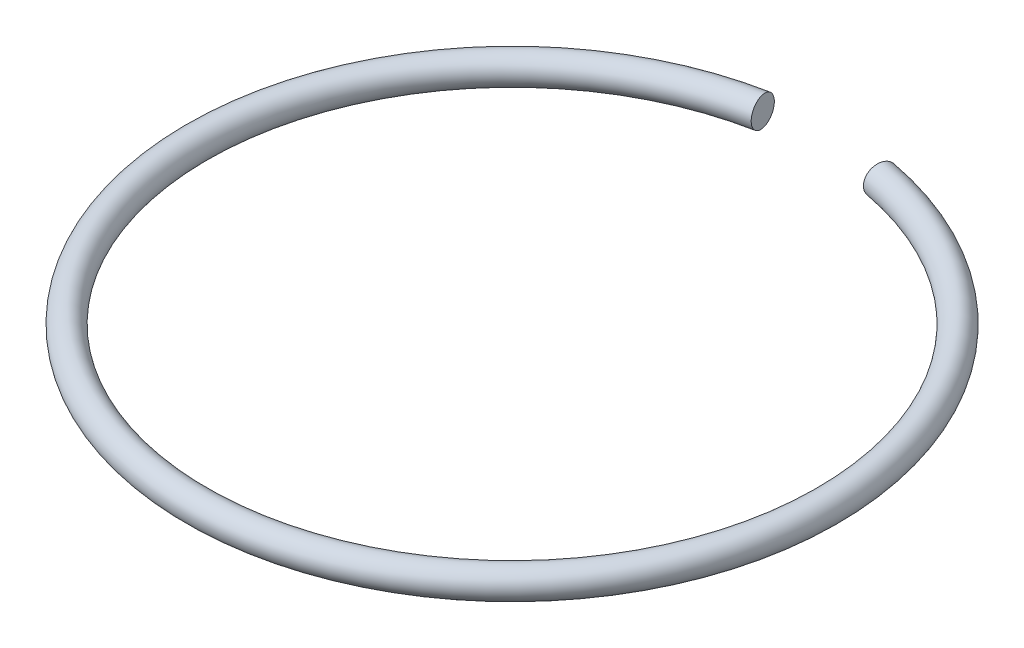
SolidWorks part; units mm, degrees
ref_plane "Plano frontal" through (0, 0, 0) normal (0, 0, 1) x (1, 0, 0)
ref_plane "Plano superior" through (0, 0, 0) normal (0, 1, 0) x (1, 0, 0)
ref_plane "Plano direito" through (0, 0, 0) normal (1, 0, 0) x (0, 0, -1)
sketch "Esboço1" plane through (0, 0, 0) normal (0, 0, 1) x (1, 0, 0)
  line L0 (0, -35.5051) -> (0, 46.7425) construction
  circle A0 centre (32.5, 5.6187) radius 1.5
  dimension "D1" = 3
  dimension "D2" = 32.5
revolve "Revolução1" add sketch "Esboço1" angle 360 about L0
sketch "Esboço2" plane through (0, 0, 0) normal (0, 1, 0) x (1, 0, 0)
  line L0 (0, 0) -> (0, 21.4783) construction
  line L1 (0, 0) -> (7.5, 39.472)
  line L2 (0, 0) -> (-7.5, 39.472)
  line L3 (-7.5, 39.472) -> (7.5, 39.472)
extrude "Corte-extrusão1" cut sketch "Esboço2" against normal blind 10 and the other way blind 10
